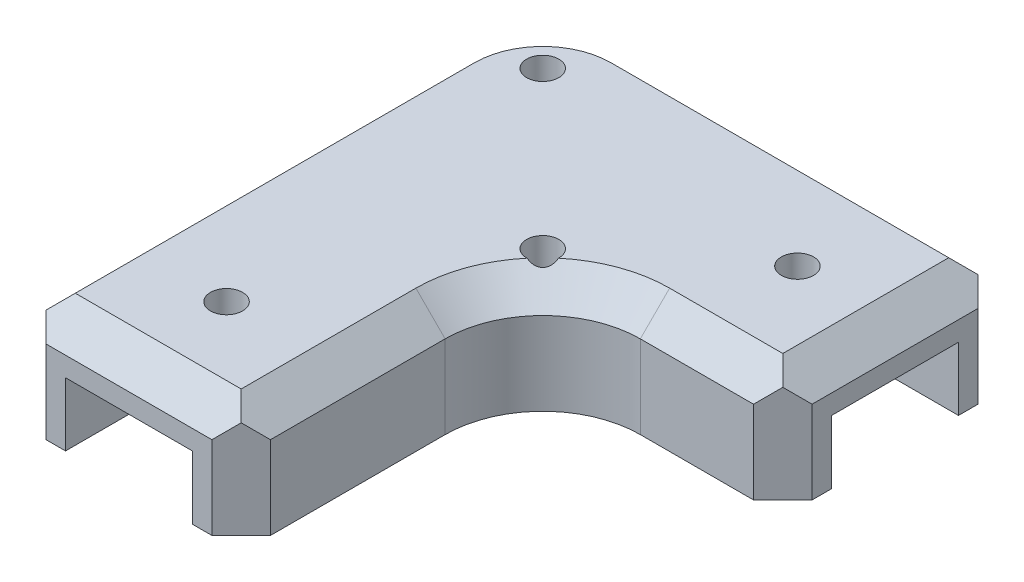
SolidWorks part; units mm, degrees
ref_plane "前视基准面" through (0, 0, 0) normal (0, 0, 1) x (1, 0, 0)
ref_plane "上视基准面" through (0, 0, 0) normal (0, 1, 0) x (1, 0, 0)
ref_plane "右视基准面" through (0, 0, 0) normal (1, 0, 0) x (0, 0, -1)
sketch "草图1" plane through (0, 0, 0) normal (0, 0, 1) x (1, 0, 0)
  line L1 (0, 0) -> (13, 0)
  line L2 (0, 0) -> (0, 13)
  line L3 (0, 13) -> (13, 13)
  line L4 (13, 0) -> (13, 13)
  line L5 (-5, 18) -> (18, 18)
  line L6 (-5, 18) -> (-5, -5)
  line L7 (-5, -5) -> (18, -5)
  line L8 (18, 18) -> (18, -5)
  dimension "D1" = 13
  dimension "D2" = 13
  dimension "D3" = 23
  dimension "D4" = 23
  dimension "D5" = 5
  dimension "D6" = 5
extrude "凸台-拉伸1" add sketch "草图1" along normal blind 53.9
sketch "草图2" plane through (0, -5, 0) normal (0, -1, 0) x (1, 0, 0)
  line L0 (-5, 53.9) -> (18, 53.9) construction
  line L1 (-5, 53.9) -> (-5, 0) construction
  circle A0 centre (6.5, 43.9) radius 1.65
  dimension "D1" = 3.3
  dimension "D2" = 10
  dimension "D3" = 11.5
extrude "切除-拉伸1" cut sketch "草图2" against normal blind 34
sketch "草图3" [suppressed] plane through (0, 25, 0) normal (0, 1, 0) x (1, 0, 0)
  line L0 (25, 0) -> (-5, 0) construction
  line L1 (2.5796, -2) -> (18.5796, -2)
  line L2 (2.5796, -2) -> (2.5796, -16)
  line L3 (2.5796, -16) -> (18.5796, -16)
  line L4 (18.5796, -2) -> (18.5796, -16)
  dimension "D1" = 14
  dimension "D2" = 2
  dimension "D3" = 16
sketch "草图4" plane through (18, 0, 0) normal (1, 0, 0) x (0, 0, -1)
  line L0 (-53.9, -5) -> (0, -5) construction
  line L1 (0, 18) -> (-23, 18)
  line L2 (0, 18) -> (0, -5)
  line L3 (0, -5) -> (-23, -5)
  line L4 (-23, 18) -> (-23, -5)
  circle A0 centre (-11.5, 6.5) radius 3
  dimension "D2" = 11.5
  dimension "D3" = 11.5
  dimension "D4" = 6
  dimension "D1" = 23
extrude "凸台-拉伸2" add sketch "草图4" along normal blind 14.6
sketch "草图5" plane through (32.6, 0, 0) normal (1, 0, 0) x (0, 0, -1)
  line L0 (0, -5) -> (0, 18) construction
  line L1 (-5, 0) -> (-18, 0)
  line L2 (-5, 0) -> (-5, 13)
  line L3 (-5, 13) -> (-18, 13)
  line L4 (-18, 0) -> (-18, 13)
  line L5 (-5, 0) -> (-18, 13) construction
  line L6 (-5, 13) -> (-18, 0) construction
  line L7 (-23, -5) -> (0, -5) construction
  point P0 (-11.5, 6.5)
  dimension "D1" = 13
  dimension "D2" = 13
  dimension "D3" = 5
  dimension "D4" = 5
extrude "拉伸-薄壁1" add sketch "草图5" along normal blind 10 thin thin type one direction wall 5
sketch "草图6" plane through (0, 18, 0) normal (0, 1, 0) x (1, 0, 0)
  line L0 (42.6, 0) -> (42.6, -23) construction
  line L1 (42.6, 0) -> (-5, 0) construction
  circle A0 centre (32.6, -11.5) radius 1.65
  dimension "D1" = 3.3
  dimension "D2" = 10
  dimension "D3" = 11.5
extrude "切除-拉伸2" cut sketch "草图6" against normal blind 39
sketch "草图7" plane through (32.6, 0, 0) normal (1, 0, 0) x (0, 0, -1)
  line L1 (-18, 13) -> (-5, 13)
  line L2 (-18, 13) -> (-18, 0)
  line L3 (-18, 0) -> (-5, 0)
  line L4 (-5, 13) -> (-5, 0)
extrude "切除-拉伸3" cut sketch "草图7" against normal blind 24.6
chamfer "倒角1" distance 3 angle 45 1 edges at (13, 6.5, 18)
chamfer "倒角2" [suppressed] distance 3 angle 45
sketch "草图8" plane through (0, -5, 0) normal (0, -1, 0) x (1, 0, 0)
  line L1 (-5, 53.9) -> (42.6, 53.9)
  line L2 (-5, 53.9) -> (-5, 0)
  line L3 (-5, 0) -> (42.6, 0)
  line L4 (42.6, 53.9) -> (42.6, 0)
extrude "切除-拉伸4" cut sketch "草图8" against normal blind 11.5
sketch "草图9" plane through (0, 13, 0) normal (0, -1, 0) x (1, 0, 0)
  line L0 (13, 5) -> (0, 18)
  line L2 (0, 18) -> (0, 0)
  line L3 (0, 0) -> (13, 0)
  line L4 (13, 0) -> (13, 5)
  dimension "D1" = 18
extrude "凸台-拉伸3" add sketch "草图9" along normal blind 6.5
fillet "圆角1" radius 10 1 edges at (-5, 12.25, 0)
fillet "圆角2" radius 10 1 edges at (18, 12.25, 23)
sketch "草图10" plane through (0, 6.5, 0) normal (0, -1, 0) x (1, 0, 0)
  line L0 (-5, 53.9) -> (-5, 10) construction
  line L1 (5, 0) -> (42.6, 0) construction
  line L2 (42.6, 18) -> (16, 18) construction
  line L3 (13, 21) -> (13, 53.9) construction
  circle A0 centre (2, 7) radius 1.65
  circle A1 centre (18, 23) radius 1.65
  dimension "D1" = 7
  dimension "D2" = 7
  dimension "D3" = 3.3
  dimension "D4" = 5
  dimension "D5" = 5
  dimension "D6" = 3.3
extrude "切除-拉伸5" cut sketch "草图10" against normal blind 28.5
chamfer "倒角3" distance 3 angle 45 6 edges at (18, 18, 43.45) (35.3, 18, 23) (20.9289, 18, 25.9289) (23.8, 18, 0) (-2.0711, 18, 2.9289) (-5, 18, 31.95)
chamfer "倒角4" distance 3 angle 45 2 edges at (42.6, 18, 11.5) (6.5, 18, 53.9)
chamfer "倒角5" distance 3 angle 45 4 edges at (42.6, 10.75, 0) (42.6, 10.75, 23) (18, 10.75, 53.9) (-5, 10.75, 53.9)
